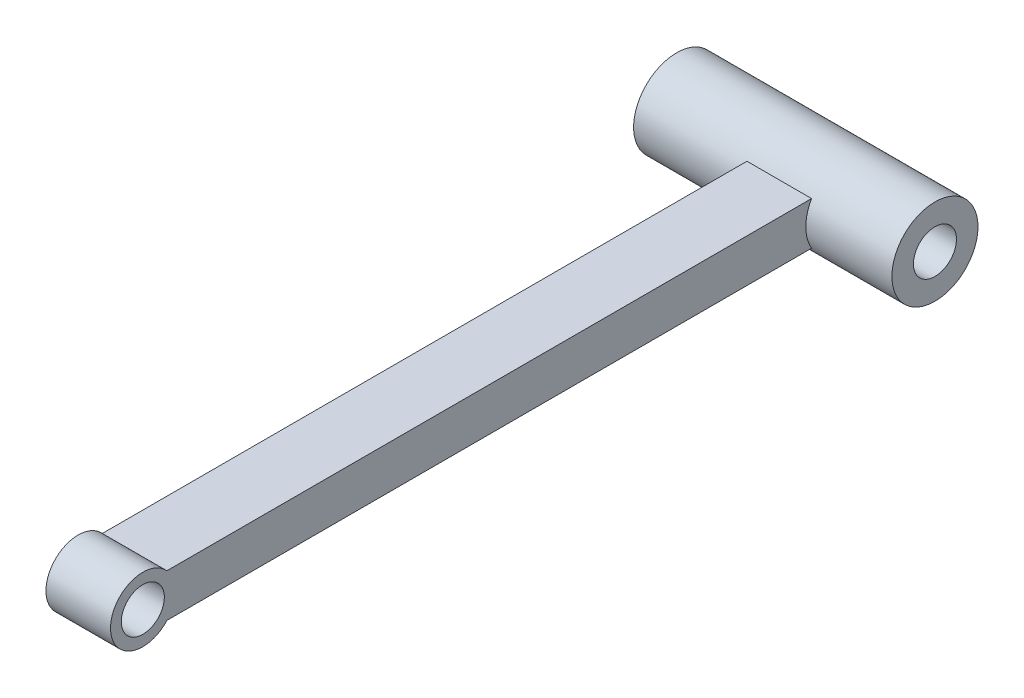
SolidWorks part; units mm, degrees
ref_plane "Front Plane" through (0, 0, 0) normal (0, 0, 1) x (1, 0, 0)
ref_plane "Top Plane" through (0, 0, 0) normal (0, 1, 0) x (1, 0, 0)
ref_plane "Right Plane" through (0, 0, 0) normal (1, 0, 0) x (0, 0, -1)
sketch "Sketch1" plane through (0, 0, 0) normal (1, 0, 0) x (0, 0, -1)
  circle A0 centre (0, 0) radius 5
  circle A1 centre (0, 0) radius 10
  dimension "D1" = 10
  dimension "D2" = 20
extrude "Boss-Extrude1" add sketch "Sketch1" along normal blind 60
sketch "Sketch2" plane through (0, 0, 0) normal (-1, 0, 0) x (0, 0, 1)
  line L0 (158.4098, 5) -> (8.6603, 5)
  line L1 (158.4098, -5) -> (8.6603, -5)
  arc A0 (158.4098, -5) -> (158.4098, 5) centre (164, 0) ccw
  circle A1 centre (0, 0) radius 10 construction
  circle A2 centre (164, 0) radius 5
  circle M3 centre (0, 0) radius 10
  dimension "D3" = 15
  dimension "D4" = 10
  dimension "D1" = 164
  dimension "D2" = 10
extrude "Boss-Extrude2" add sketch "Sketch2" against normal blind 15 separate body contours L1 A0 L0 A2 M3 region at (0, 0, 88.3666)
move or copy body "Body-Move/Copy1" bodies to move or copy 102 copy no translate (25, 0, 0) parameters "D1"=25, "D2"=0, "D3"=0
ref_axis "Axis1" through (60, 0, 0) along (-1, 0, 0)
ref_axis "Axis2" through (40, 0, 164) along (-1, 0, 0)
